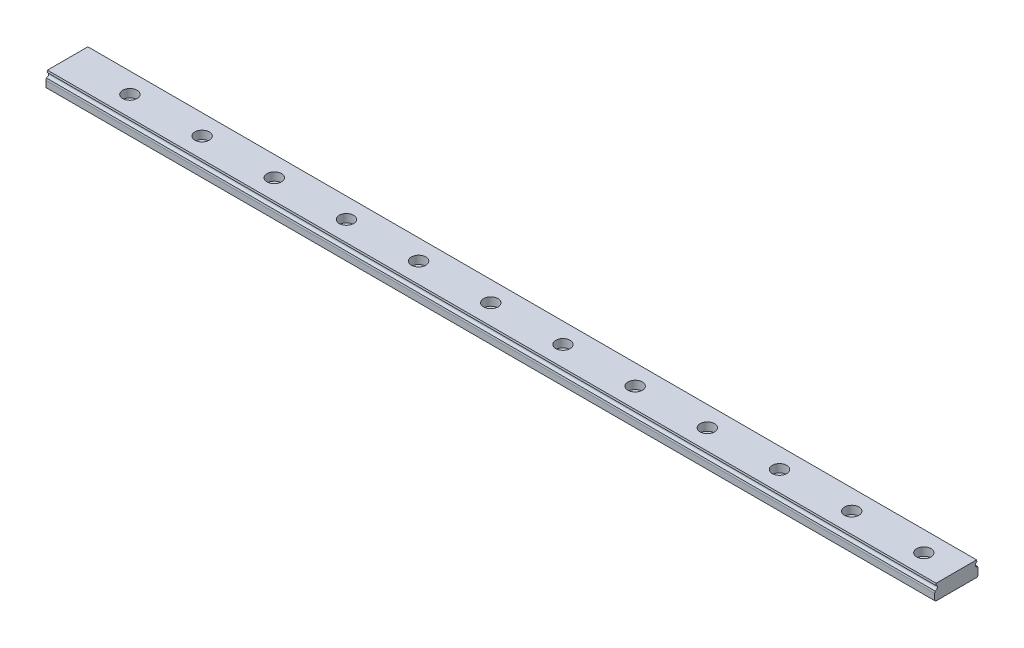
SolidWorks part; units mm, degrees
ref_plane "Plano frontal" through (0, 0, 0) normal (0, 0, 1) x (1, 0, 0)
ref_plane "Plano superior" through (0, 0, 0) normal (0, 1, 0) x (1, 0, 0)
ref_plane "Plano direito" through (0, 0, 0) normal (1, 0, 0) x (0, 0, -1)
ref_plane "Plano1" through (-15, 0, 0) normal (1, 0, 0) x (0, 0, -1)
sketch "Esboço1" plane through (-15, 0, 0) normal (1, 0, 0) x (0, 0, -1)
  line L0 (-12, 4) -> (-12, 0.5)
  line L1 (-12, 0.5) -> (-11.5, 0)
  line L2 (-11.5, 0) -> (11.5, 0)
  line L3 (11.5, 0) -> (12, 0.5)
  line L4 (12, 0.5) -> (12, 4)
  line L5 (12, 4) -> (11.8146, 5.0517)
  line L6 (11.3837, 7.4951) -> (11.2065, 8.5)
  line L7 (11.2065, 8.5) -> (-11.2065, 8.5)
  line L8 (-11.2065, 8.5) -> (-11.3837, 7.4951)
  line L9 (-11.8146, 5.0517) -> (-12, 4)
  arc A0 (11.8146, 5.0517) -> (11.3837, 7.4951) centre (11.75, 6.3) cw
  arc A1 (-11.3837, 7.4951) -> (-11.8146, 5.0517) centre (-11.75, 6.3) cw
extrude "Ressalto-extrusão1" add sketch "Esboço1" along normal blind 353 and the other way blind 139.5
ref_plane "Plano2" through (0, 0, 0) normal (0, 0, 1) x (1, 0, 0)
sketch "Esboço2" plane through (0, 0, 0) normal (0, 0, 1) x (1, 0, 0)
  line L0 (0, 8.5) -> (4, 8.5)
  line L1 (4, 8.5) -> (4, 4)
  line L2 (4, 4) -> (2.25, 4)
  line L3 (2.25, 4) -> (2.25, 0)
  line L4 (2.25, 0) -> (0, 0)
  line L5 (0, 0) -> (0, 8.5)
  line L6 (0, 0) -> (0, 8.5) construction
ref_plane "Plano3" through (0, 0, 0) normal (0, 0, 1) x (1, 0, 0)
sketch "Esboço3" plane through (0, 0, 0) normal (0, 0, 1) x (1, 0, 0)
  line L0 (40, 8.5) -> (44, 8.5)
  line L1 (44, 8.5) -> (44, 4)
  line L2 (44, 4) -> (42.25, 4)
  line L3 (42.25, 4) -> (42.25, 0)
  line L4 (42.25, 0) -> (40, 0)
  line L5 (40, 0) -> (40, 8.5)
  line L6 (40, 0) -> (40, 8.5) construction
revolve "Corte-Revolução2" cut sketch "Esboço3" angle 360 about L6 reverse direction yes
pattern_linear "LPattern1" count 8 spacing 40 along (1, 0, 0) count 5 spacing 40 along (-1, 0, 0) of "Corte-Revolução2"
